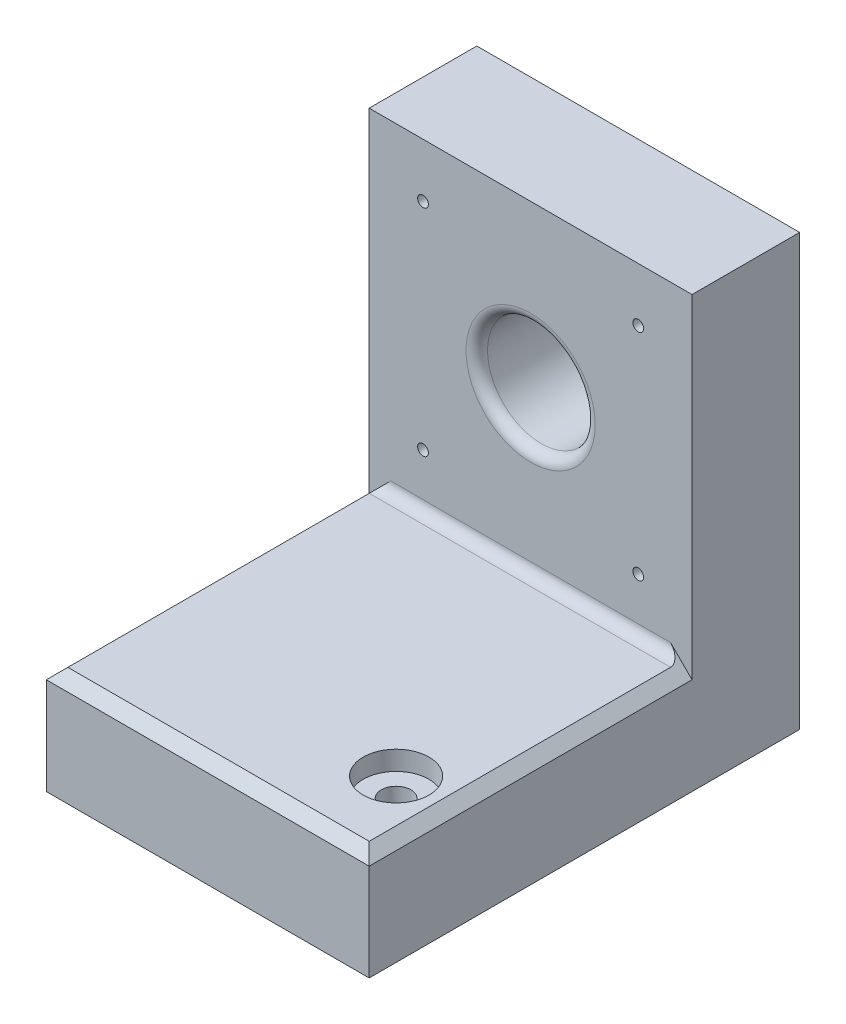
SolidWorks part; units mm, degrees
ref_plane "Front" through (0, 0, 0) normal (0, 0, 1) x (1, 0, 0)
ref_plane "Top" through (0, 0, 0) normal (0, 1, 0) x (1, 0, 0)
ref_plane "Right" through (0, 0, 0) normal (1, 0, 0) x (0, 0, -1)
sketch "Sketch1" plane through (0, 0, 0) normal (0, 1, 0) x (1, 0, 0)
  line L0 (0, 0) -> (0, 20)
  line L1 (0, 20) -> (60, 20)
  line L2 (60, 20) -> (60, 0)
  line L3 (60, 0) -> (0, 0)
  line L4 (0, 0) -> (0, -60)
  line L5 (0, -60) -> (60, -60)
  line L6 (60, -60) -> (60, 0)
  dimension "D1" = 60
  dimension "D2" = 20
  dimension "D3" = 60
extrude "Boss-Extrude1" add sketch "Sketch1" along normal blind 20 contours L5 L6 L3 L4 region at (30, 0, 30)
extrude "Boss-Extrude2" add sketch "Sketch1<3>" along normal blind 80 contours L3 L2 L1 L0 region at (30, 0, -10)
sketch "Sketch1<3>" plane through (0, 0, 0) normal (0, 1, 0) x (1, 0, 0) same geometry as "Sketch1"
sketch "Sketch3" plane through (0, 0, 0) normal (0, 0, 1) x (1, 0, 0)
  line L0 (0, 80) -> (30, 80) construction
  line L1 (60, 80) -> (0, 80) construction
  line L2 (30, 80) -> (30, 50) construction
  circle A0 centre (30, 50) radius 10
  dimension "D2" = 20
  dimension "D1" = 30
extrude "Cut-Extrude2" cut sketch "Sketch3" against normal through all
fillet "Fillet2" radius 2 2 edges at (40, 50, -20) (40, 50, 0)
sketch "Sketch4" plane through (0, 0, 0) normal (0, 0, 1) x (1, 0, 0)
  line L0 (0, 80) -> (10, 80) construction
  line L1 (60, 80) -> (0, 80) construction
  line L2 (10, 80) -> (10, 70) construction
  line L3 (10, 70) -> (10, 30) construction
  line L4 (10, 30) -> (50, 30) construction
  line L5 (50, 30) -> (50, 70) construction
  line L6 (50, 70) -> (10, 70) construction
  circle A0 centre (10, 70) radius 1
  circle A1 centre (50, 70) radius 1
  circle A2 centre (50, 30) radius 1
  circle A3 centre (10, 30) radius 1
  dimension "D5" = 2
  dimension "D6" = 2
  dimension "D7" = 2
  dimension "D8" = 2
  dimension "D1" = 10
  dimension "D2" = 10
  dimension "D3" = 40
  dimension "D4" = 40
extrude "Cut-Extrude3" cut sketch "Sketch4" against normal blind 10
sketch "Sketch7" plane through (0, 20, 0) normal (0, 1, 0) x (1, 0, 0)
  line L0 (60, -60) -> (60, -45) construction
  line L1 (60, -60) -> (60, 0) construction
  line L2 (60, -45) -> (50, -45) construction
  circle A0 centre (50, -45) radius 6.12
  dimension "D3" = 12.24
  dimension "D1" = 10
  dimension "D2" = 15
extrude "Cut-Extrude5" cut sketch "Sketch7" against normal blind 3.58
sketch "Sketch8" plane through (0, 16.42, 0) normal (0, 1, 0) x (1, 0, 0)
  circle A0 centre (50, -45) radius 2.75
  dimension "D1" = 5.5
extrude "Cut-Extrude6" cut sketch "Sketch8" against normal through all
sketch "Sketch9" plane through (0, 0, 60) normal (0, 0, 1) x (1, 0, 0)
  line L0 (0, 20) -> (2, 20)
  line L1 (0, 20) -> (60, 20) construction
  line L3 (0, 20) -> (0, 0) construction
  line L4 (0, 18) -> (0, 20)
  line L5 (2, 20) -> (0, 18)
  line L6 (60, 20) -> (58, 20)
  line L7 (58, 20) -> (60, 18)
  line L8 (60, 20) -> (60, 0) construction
  line L9 (60, 20) -> (60, 18)
  point P11 (0, 0)
  dimension "D1" = 2
  dimension "D3" = 2
extrude "Cut-Extrude7" cut sketch "Sketch9" against normal blind 60
fillet "Fillet7" radius 2 1 edges at (30, 20, 0)
sketch "Sketch11" plane through (60, 0, 0) normal (1, 0, 0) x (0, 0, -1)
  line L0 (-60, 20) -> (-58, 20)
  line L1 (-2, 20) -> (-60, 20) construction
  line L2 (-60, 20) -> (-60, 18)
  line L3 (0, 18) -> (-60, 18) construction
  line L4 (-60, 18) -> (-60, 0) construction
  line L5 (-60, 18) -> (-58, 20)
  point P5 (0, 0)
  dimension "D1" = 2
extrude "Cut-Extrude13" cut sketch "Sketch11" against normal blind 60
